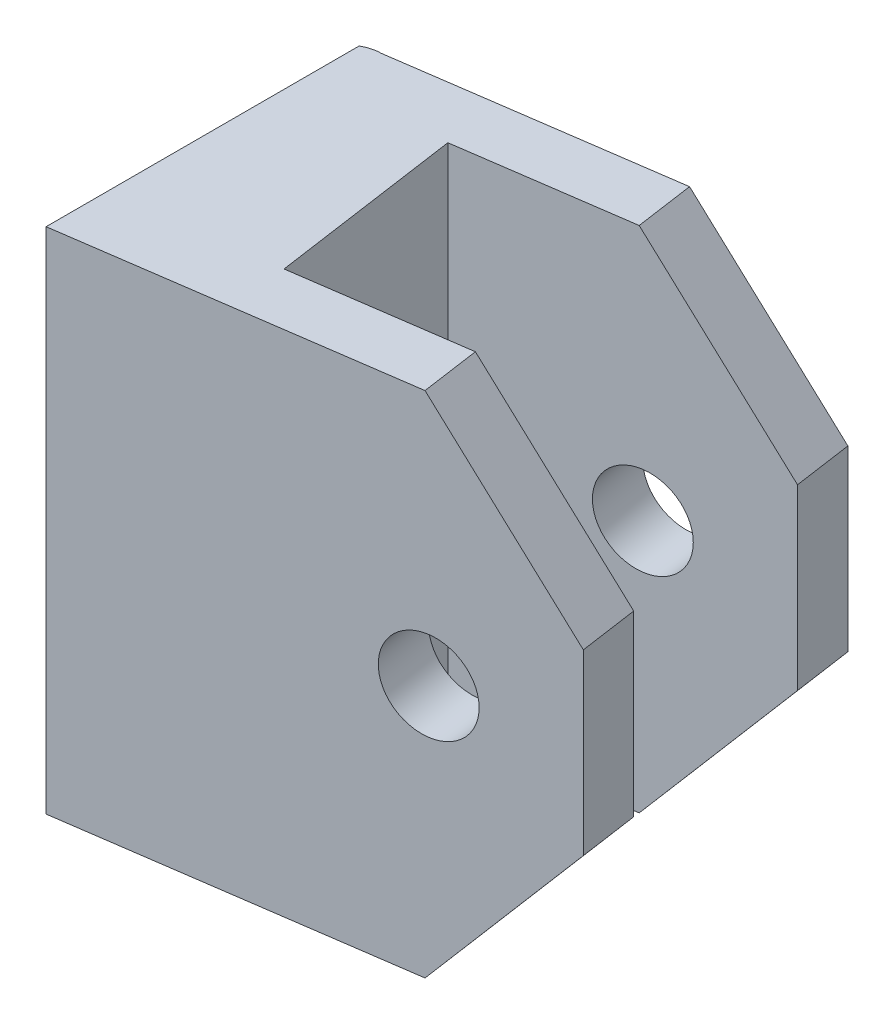
SolidWorks part; units mm, degrees
material "Custom Plastic"
ref_plane "X-Y Datum" through (0, 0, 0) normal (0, 0, 1) x (1, 0, 0)
ref_plane "X-Z Datum" through (0, 0, 0) normal (0, 1, 0) x (1, 0, 0)
ref_plane "Y-Z Datum" through (0, 0, 0) normal (1, 0, 0) x (0, 0, -1)
sketch "Sketch1" plane through (0, 0, 0) normal (0, 1, 0) x (1, 0, 0)
  line L10 (43.5767, 6.2522) -> (0, 0)
  line L11 (31.488, -12.3281) -> (6.9122, -15.8541) construction
  line L12 (31.488, -12.3281) -> (37.2397, -52.4164) construction
  line L13 (47.4113, -20.4743) -> (14.7261, -25.1639)
  line L14 (14.7261, -25.1639) -> (11.7933, -4.723)
  line L15 (11.7933, -4.723) -> (44.4786, -0.0334)
  line L16 (47.4113, -20.4743) -> (48.3132, -26.7599)
  line L17 (48.3132, -26.7599) -> (-0.0216, -33.6948)
  line L19 (44.4786, -0.0334) -> (43.5767, 6.2522)
  line L23 (-1.905, -33.8451) -> (-1.905, 10.9886) construction
  line L24 (-1.905, -0.5148) -> (-1.905, -33.8451)
  line L25 (-0.0216, -33.6948) -> (-1.905, -33.965)
  line L26 (-1.905, -33.965) -> (-1.905, -33.8451)
  arc A0 (0, 0) -> (-1.905, -0.5148) centre (0, -3.7822) ccw
  point P0 (31.488, -12.3281)
  point P14 (0, 0)
  dimension "D1" = 18.415
  dimension "D2" = 31.488
  dimension "D3" = 50.7324
  dimension "D5" = 10.3251
  dimension "D6" = 10.3251
  dimension "D7" = 14.605
  dimension "D8" = 6.35
  dimension "D9" = 6.35
extrude "Boss-Extrude1" add sketch "Sketch1" along normal blind 54.3789
sketch "Sketch6" plane through (4.7364, 0, 33.0121) normal (0.142, 0, 0.9899) x (0.9899, 0, -0.142)
  line L0 (-6.7095, 54.3789) -> (44.023, 54.3789) construction
  line L1 (44.023, 36.7144) -> (29.0719, 54.3789)
  line L2 (44.023, 54.3789) -> (44.023, 0) construction
  line L3 (29.0719, 54.3789) -> (44.023, 54.3789)
  line L4 (44.023, 54.3789) -> (44.023, 36.7144)
  line L5 (29.418, 27.1894) -> (40.6527, 27.1894) construction
  line L6 (44.023, 0) -> (44.023, 17.6644)
  line L7 (29.0719, 0) -> (44.023, 0)
  line L8 (44.023, 17.6644) -> (29.0719, 0)
  circle A0 centre (29.418, 27.1894) radius 4.7625
  dimension "D1" = 9.525
  dimension "D2" = 27.1894
  dimension "D3" = 19.05
extrude "Cut-Extrude2" cut sketch "Sketch6" against normal through all
sketch "Sketch9" plane through (-1.905, 0, 0) normal (-1, 0, 0) x (0, 0, 1)
  point P0 (17.8317, 14.4894)
  point P1 (17.8317, 39.8894)
hole_wizard "M8x1.0 Tapped Hole1" positions "Sketch10" profile "Sketch12" tap size "M8x1.0" standard "ANSI Metric"
sketch "Sketch10" plane through (-1.905, 0, 0) normal (-1, 0, 0) x (0, 0, 1)
  point P0 (17.8317, 14.4894)
  point P3 (17.8317, 39.8894)
sketch "Sketch12" plane through (-1.905, 14.4894, 17.8317) normal (0, 1, 0) x (0, 0, 1)
  line L0 (0, 0) -> (0, 16)
  line L1 (0, 16) -> (3.5, 13.897)
  line L2 (3.5, 13.897) -> (3.5, 0)
  line L5 (3.5, 0) -> (0, 0)
  line L10 (0, 16) -> (-3.5, 13.897) construction
  line L11 (0, -6.35) -> (0, 107.95) construction
  dimension "Tap Drill Dia." = 7
  dimension "Tap Drill Depth" = 16
  dimension "Drill Angle" = 118
cosmetic thread "Hole Thread1" parameters "D1"=16.002, "D2"=8
cosmetic thread "Hole Thread2" parameters "D1"=16.002, "D2"=8
